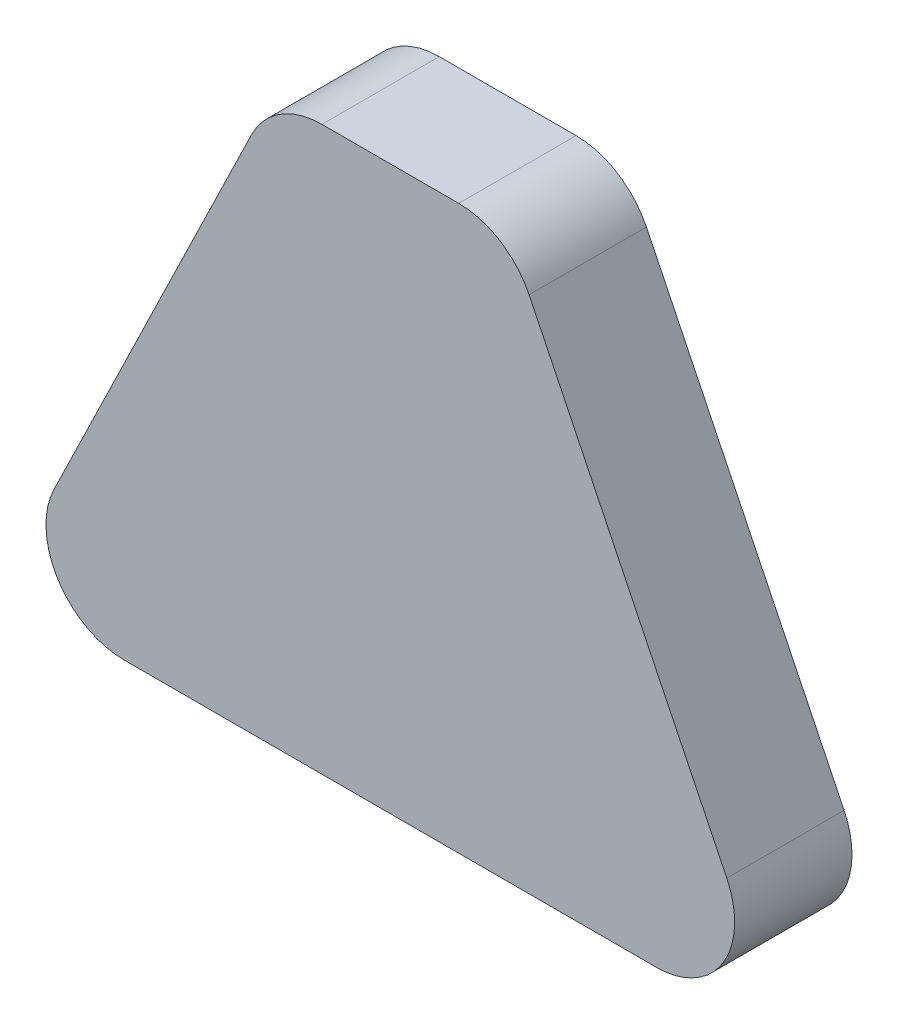
SolidWorks part; units mm, degrees
ref_plane "Front Plane" through (0, 0, 0) normal (0, 0, 1) x (1, 0, 0)
ref_plane "Top Plane" through (0, 0, 0) normal (0, 1, 0) x (1, 0, 0)
ref_plane "Right Plane" through (0, 0, 0) normal (1, 0, 0) x (0, 0, -1)
sketch "Sketch1" plane through (0, 0, 0) normal (0, 0, 1) x (1, 0, 0)
  line L0 (-50, 0) -> (-15, 71.9375)
  line L1 (-15, 71.9375) -> (15, 71.9375)
  line L3 (50, 0) -> (-50, 0)
  line L4 (0, 73.0285) -> (0, 24.2987) construction
  line L5 (50, 0) -> (15, 71.9375)
  point P4 (-35.7545, 0.6605)
  point P8 (0, 0)
  point P9 (0, 71.9375)
  point P10 (0, 0)
  dimension "D1" = 15
  dimension "D2" = 80
  dimension "D3" = 50
extrude "Boss-Extrude1" add sketch "Sketch1" along normal blind 15 contours L5 L1 L0 L3
fillet "Fillet1" radius 10 4 edges at (-50, 0, 7.5) (50, 0, 7.5) (15, 71.9375, 7.5) (-15, 71.9375, 7.5)
